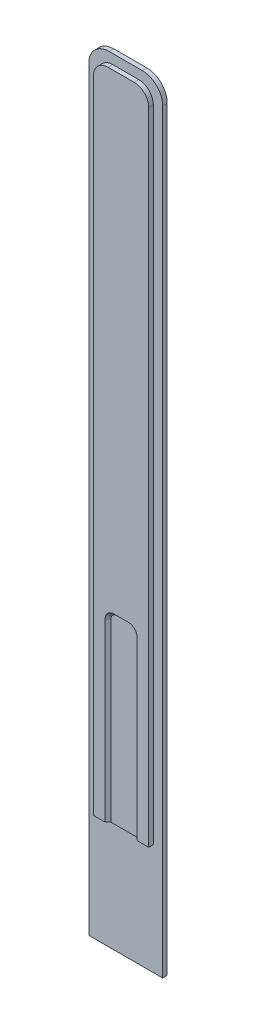
SolidWorks part; units mm, degrees
ref_plane "Front" through (0, 0, 0) normal (0, 0, 1) x (1, 0, 0)
ref_plane "Top" through (0, 0, 0) normal (0, 1, 0) x (1, 0, 0)
ref_plane "Right" through (0, 0, 0) normal (1, 0, 0) x (0, 0, -1)
ref_plane "new front for the battle" through (0, 0, 250.461) normal (0, 0, 1) x (1, 0, 0)
sketch "Sketch1" plane through (0, 0, 250.461) normal (0, 0, 1) x (1, 0, 0)
  line L0 (-76.9, -219) -> (-26.1, -219) construction
  line L1 (-62.9, 238.2) -> (-40.1, 238.2)
  line L2 (-76.9, 224.2) -> (-76.9, -219)
  line L4 (-26.1, 224.2) -> (-26.1, -219)
  line L5 (-76.9, 238.2) -> (-26.1, -219) construction
  line L6 (-76.9, -219) -> (-26.1, 238.2) construction
  line L8 (-76.9, -219) -> (-76.9, -295.2)
  line L9 (-76.9, -295.2) -> (-26.1, -295.2)
  line L10 (-26.1, -219) -> (-26.1, -295.2)
  arc A0 (-40.1, 238.2) -> (-26.1, 224.2) centre (-40.1, 224.2) cw
  arc A1 (-62.9, 238.2) -> (-76.9, 224.2) centre (-62.9, 224.2) ccw
  point P0 (-51.5, 9.6)
  dimension "D5" = 14
  dimension "D1" = 76.2
  dimension "D2" = 457.2
  dimension "D3" = 50.8
  dimension "D4" = 51.5
  dimension "D6" = 219
extrude "Boss-Extrude2" add sketch "Sketch1" along normal mid plane 3.175 separate body
sketch "Sketch2" plane through (0, 0, 250.461) normal (0, 0, 1) x (1, 0, 0)
  line L0 (-40.1, 238.2) -> (-62.9, 238.2) construction
  line L1 (-60.5, 231.6) -> (-42.5, 231.6)
  line L2 (-70.5, 221.6) -> (-70.5, -219)
  line L3 (-70.5, -219) -> (-32.5, -219)
  line L4 (-32.5, 221.6) -> (-32.5, -219)
  line L5 (-76.9, -219) -> (-26.1, -219) construction
  arc A0 (-42.5, 231.6) -> (-32.5, 221.6) centre (-42.5, 221.6) cw
  arc A1 (-60.5, 231.6) -> (-70.5, 221.6) centre (-60.5, 221.6) ccw
  point P4 (-51.5, 231.6)
  point P5 (-51.5, 238.2)
  point P13 (-32.5, 231.6)
  point P16 (-70.5, 231.6)
  dimension "D3" = 10
  dimension "D1" = 6.6
  dimension "D2" = 38
extrude "Boss-Extrude3" add sketch "Sketch2" along normal mid plane 9.525
sketch "Sketch3" plane through (0, 0, 255.2235) normal (0, 0, 1) x (1, 0, 0)
  line L1 (-60.5, -219) -> (-42.5, -219)
  line L2 (-60.5, -219) -> (-60.5, -98)
  line L3 (-56.5, -94) -> (-46.5, -94)
  line L4 (-42.5, -219) -> (-42.5, -98)
  line L5 (-70.5, -219) -> (-32.5, -219) construction
  arc A0 (-46.5, -94) -> (-42.5, -98) centre (-46.5, -98) cw
  arc A1 (-60.5, -98) -> (-56.5, -94) centre (-56.5, -98) cw
  point P4 (-51.5, -219)
  point P6 (-51.5, -219)
  point P10 (-42.5, -94)
  point P13 (-60.5, -94)
  point P14 (0, 0)
  dimension "D3" = 4
  dimension "D1" = 125
  dimension "D2" = 18
extrude "Cut-Extrude1" cut sketch "Sketch3" against normal blind 2
mirror "Mirror2" about plane through (0, 0, 250.461) normal (0, 0, 1) of "Cut-Extrude1"
chamfer "Chamfer1" distance 2 angle 45 10 edges at (-42.5, -158.5, 245.6985) (-60.5, -158.5, 245.6985) (-43.6716, -95.1716, 245.6985) (-59.3284, -95.1716, 245.6985) (-51.5, -94, 245.6985) (-42.5, -158.5, 255.2235) (-60.5, -158.5, 255.2235) (-43.6716, -95.1716, 255.2235) (-59.3284, -95.1716, 255.2235) (-51.5, -94, 255.2235)
